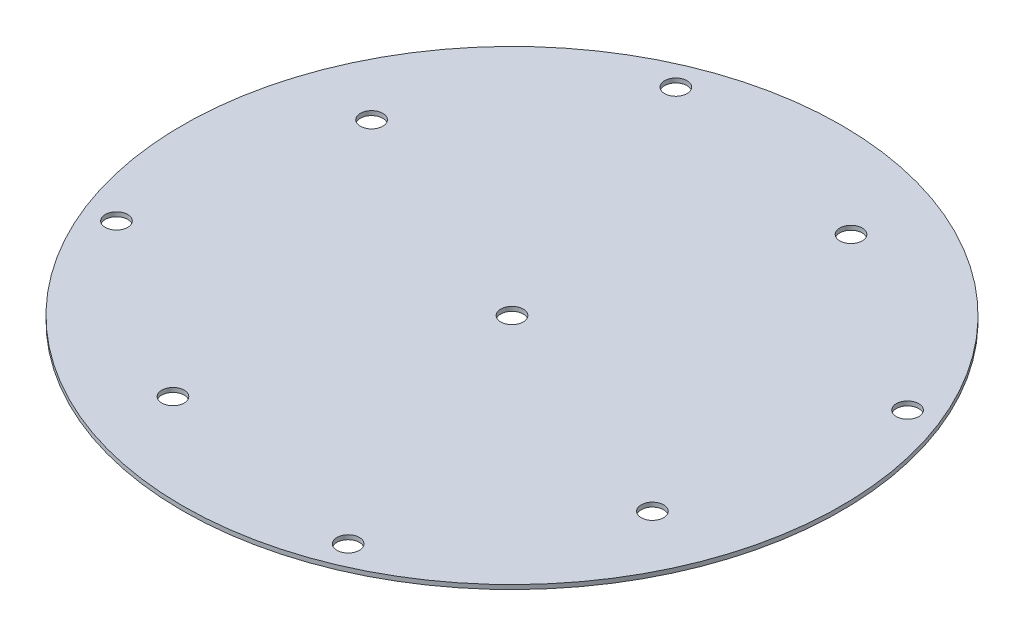
SolidWorks part; units mm, degrees
ref_plane "Front Plane" through (0, 0, 0) normal (0, 0, 1) x (1, 0, 0)
ref_plane "Top Plane" through (0, 0, 0) normal (0, 1, 0) x (1, 0, 0)
ref_plane "Right Plane" through (0, 0, 0) normal (1, 0, 0) x (0, 0, -1)
sketch "Sketch2" plane through (0, 0, 0) normal (1, 0, 0) x (0, 0, -1)
  line L0 (0, 0) -> (-76.2, 0)
  line L1 (-76.2, 0) -> (-76.2, 1)
  line L2 (-76.2, 1) -> (0, 1)
  line L5 (0, 1) -> (0, 0)
  dimension "D1" = 76.2
  dimension "D2" = 1
ref_axis "Axis1" through (0, -0.05, 0) along (0, 1, 0)
revolve "Revolve1" add sketch "Sketch2" angle 360 about axis through (0, -0.05, 0) along (0, 1, 0)
hole_wizard "#6 (0.204) Diameter Hole1" positions "Sketch6" profile "Sketch7" hole size "#6" standard "ANSI Inch" end condition through all
sketch "Sketch6" plane through (0, 1, 0) normal (0, 1, 0) x (1, 0, 0)
  line L0 (0, 0) -> (-53.438, 129.0108) construction
  line L2 (0, 0) -> (0, 109.0908) construction
  line L3 (0, 0) -> (-70.3996, 29.1605) construction
  circle A0 centre (0, 0) radius 76.2 construction
  point P0 (-26.7878, 64.6716)
  point P11 (264.7437, 73.7878)
  point P20 (-55.4328, 22.961)
  dimension "D1" = 22.5
  dimension "D2" = 70
  dimension "D3" = 60
  dimension "D4" = 45
sketch "Sketch7" plane through (-26.7878, 1, -64.6716) normal (1, 0, 0) x (0, 0, 1)
  line L0 (0, 0) -> (0, 1)
  line L1 (0, 1) -> (2.5908, 1)
  line L2 (2.5908, 1) -> (2.5908, 0)
  line L5 (2.5908, 0) -> (0, 0)
  line L11 (0, -6.35) -> (0, 107.95) construction
  dimension "Thru Hole Dia." = 5.1816
  dimension "Thru Hole Depth" = 1
pattern_circular "CirPattern3" count 4 over 360 about axis through (0, -0.05, 0) along (0, 1, 0) of "#6 (0.204) Diameter Hole1"
hole_wizard "#6 (0.204) Diameter Hole2" positions "Sketch8" profile "Sketch9" hole size "#6" standard "ANSI Inch" end condition through all
sketch "Sketch8" plane through (0, 1, 0) normal (0, 1, 0) x (1, 0, 0)
  line L0 (0, 0) -> (106.3094, -1.7118) construction
  point P7 (0, 0)
sketch "Sketch9" plane through (0, 1, 0) normal (1, 0, 0) x (0, 0, 1)
  line L0 (0, 0) -> (0, 1)
  line L1 (0, 1) -> (2.5908, 1)
  line L2 (2.5908, 1) -> (2.5908, 0)
  line L5 (2.5908, 0) -> (0, 0)
  line L11 (0, -6.35) -> (0, 107.95) construction
  dimension "Thru Hole Dia." = 5.1816
  dimension "Thru Hole Depth" = 1
equation "\"TubeDiameter\" = 6.000in"
equation "\"D1@Sketch2\"=\"TubeDiameter\"/2"
